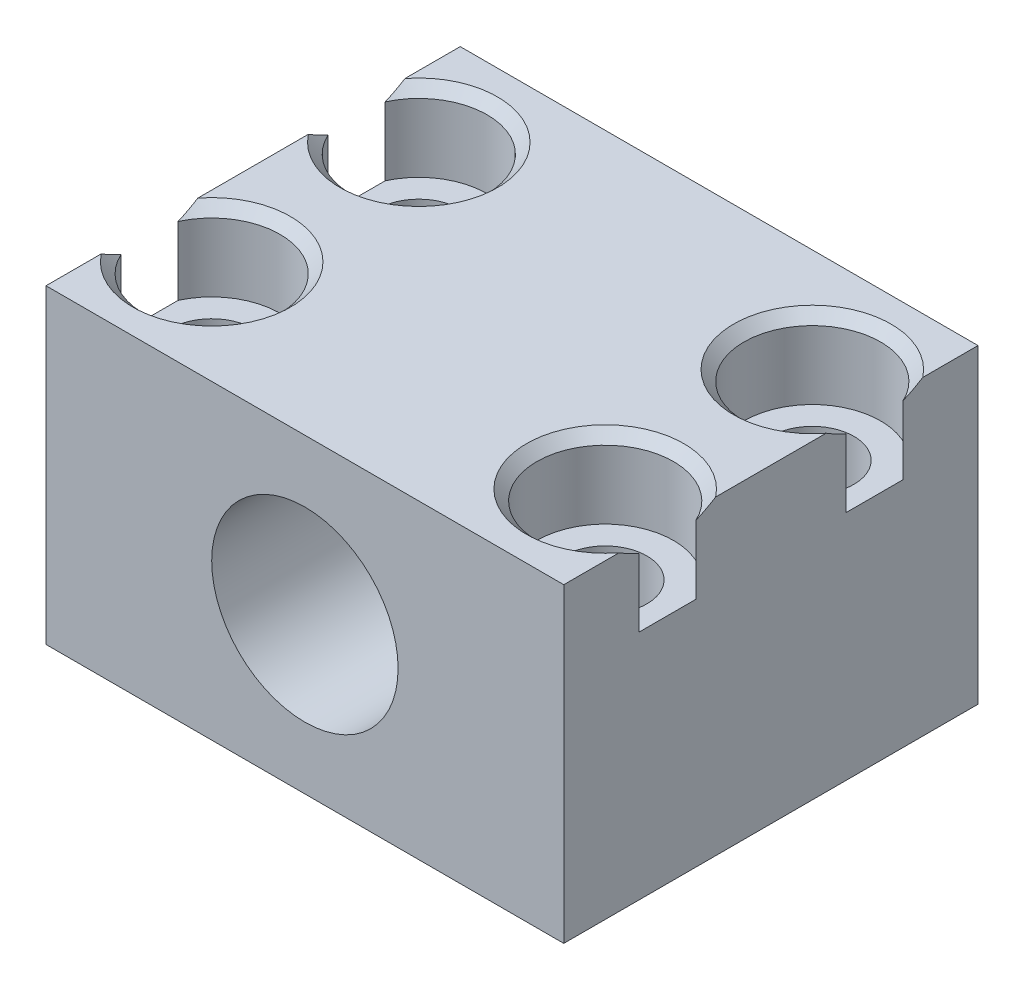
SolidWorks part; units mm, degrees
material "Gray Cast Iron"
ref_plane "Front Plane" through (0, 0, 0) normal (0, 0, 1) x (1, 0, 0)
ref_plane "Top Plane" through (0, 0, 0) normal (0, 1, 0) x (1, 0, 0)
ref_plane "Right Plane" through (0, 0, 0) normal (1, 0, 0) x (0, 0, -1)
sketch "Sketch1" plane through (0, 0, 0) normal (0, 0, 1) x (1, 0, 0)
  circle A0 centre (0, 0) radius 5.715
  circle A1 centre (0, 0) radius 18.669
  dimension "D3" = 11.43
  dimension "D1" = 37.338
extrude "nut-body-extrude" add sketch "Sketch1" along normal blind 25.4
sketch "Sketch2" plane through (0, 0, 0) normal (0, 0, 1) x (1, 0, 0)
  line L0 (0, 9.525) -> (0, 34.8179) construction
  line L1 (9.525, 0) -> (42.4926, 0) construction
  line L3 (-15.875, 9.525) -> (15.875, 9.525)
  line L4 (-15.875, 9.525) -> (-15.875, -9.525)
  line L5 (-15.875, -9.525) -> (15.875, -9.525)
  line L6 (15.875, 9.525) -> (15.875, -9.525)
  circle A1 centre (0, 0) radius 18.669
  circle A2 centre (0, 0) radius 18.669
  point P8 (-15.875, 0)
  point P9 (0, 9.525)
  dimension "D1" = 19.05
  dimension "D3" = 31.75
  dimension "D2" = 0
extrude "nut-trim-cut-extrude" cut sketch "Sketch2" along normal through all contours L3 A2 | L5 A2 | L6 A2 | L4 A2 region at (-18.141, 0, 0)
hole_wizard "CBORE for #10 Socket Head Cap Screw1" positions "Sketch5" profile "Sketch4" counterbore size "#10" standard "ANSI Inch" end condition through all
sketch "Sketch5" plane through (0, 9.525, 0) normal (0, 1, 0) x (1, 0, 0)
  line L0 (12.065, -6.35) -> (12.065, -19.05) construction
  line L1 (12.065, -19.05) -> (-12.065, -19.05) construction
  line L2 (-12.065, -19.05) -> (-12.065, -6.35) construction
  line L3 (-12.065, -6.35) -> (12.065, -6.35) construction
  line L4 (0, 0) -> (0, -12.7) construction
  line L5 (0, -12.7) -> (15.875, -12.7) construction
  line L6 (15.875, -25.4) -> (15.875, 0) construction
  line L7 (-5.715, 0) -> (-5.715, -25.4) construction
  line L8 (-5.715, 0) -> (-5.715, -25.4) construction
  line L9 (5.715, 0) -> (5.715, -25.4) construction
  point P0 (12.065, -6.35)
  point P2 (12.065, -19.05)
  point P4 (-12.065, -19.05)
  point P6 (-12.065, -6.35)
  point P29 (12.065, -12.7)
  point P43 (0, -6.35)
  dimension "D1" = 24.13
  dimension "D2" = 12.7
sketch "Sketch4" plane through (12.065, 9.525, 6.35) normal (1, 0, 0) x (0, 0, 1)
  line L0 (0, 0) -> (0, 19.05)
  line L1 (0, 19.05) -> (2.5527, 19.05)
  line L3 (2.5527, 19.05) -> (2.5527, 4.826)
  line L4 (4.191, 4.826) -> (2.5527, 4.826)
  line L5 (4.191, 4.826) -> (4.191, 0.635)
  line L6 (4.191, 0.635) -> (4.826, 0)
  line L7 (4.826, 0) -> (0, 0)
  line L8 (-4.191, 0.635) -> (-4.826, 0) construction
  line L11 (0, -6.35) -> (0, 107.95) construction
  dimension "Thru Hole Dia." = 5.1054
  dimension "Thru Hole Depth" = 19.05
  dimension "C'Bore Dia." = 8.382
  dimension "C'Bore Depth" = 4.826
  dimension "Near C'Sink Dia." = 9.652
  dimension "Near C'Sink Angle" = 90
equation "\"dovetail-angle\" = 55"
equation "\"dovetail-stock-width\" = 5"
equation "\"dovetail-stock-height\" = 1.25"
equation "\"dovetail-depth\" = 0.5 * \"dovetail-stock-height\""
equation "\"dovetail-throat-width\" = \"dovetail-stock-width\" - (2 * \"dovetail-depth\")"
equation "\"delta-x\" = 6"
equation "\"delta-y\" = 3"
equation "\"gib-thickness\" = 0.25"
equation "\"x-slide-length\" = \"dovetail-stock-width\" + \"delta-x\""
equation "\"y-slide-length\" = \"dovetail-stock-width\" + \"delta-y\""
equation "\"dog-point-diam\" = .149"
equation "\"dog-point-length\" = .067"
equation "\"dovetail-double-height\" = 2 * \"dovetail-depth\" + 0.5"
equation "\"acme-major-diam\" = .5"
equation "\"acme-pitch-diam\" = 0.45"
equation "\"acme-minor-diam\" = 0.4"
equation "\"acme-nut-od\" = 1.47"
equation "\"acme-nut-length\" = 1"
equation "\"D3@Sketch1\"=\"acme-pitch-diam\""
equation "\"D1@Sketch1\"=\"acme-nut-od\""
equation "\"D1@nut-body-extrude\"=\"acme-nut-length\""
equation "\"acme-nut-trim-height\" = .75"
equation "\"D1@Sketch2\"=\"acme-nut-trim-height\""
equation "\"screw-bearing-od\" = 0.5"
equation "\"screw-bearing-length\" = .375"
equation "\"screw-bearing-id\" = .375"
equation "\"end-plate-thickness\" = \"screw-bearing-length\""
equation "\"screw-add-length\" = 2 * \"end-plate-thickness\" + 1 + 0.5"
equation "\"x-screw-length\" = \"x-slide-length\" + \"screw-add-length\""
equation "\"y-screw-length\" = \"y-slide-length\" + \"screw-add-length\""
equation "\"acme-nut-mount-hole-space-vert\" = 0.5 * \"acme-nut-length\""
equation "\"D2@Sketch5\"=\"acme-nut-mount-hole-space-vert\""
equation "\"vise-hole-center-dist\" = 6.75"
equation "\"wiper_plate_clearance\" = .03"
equation "\"dial-width\" = 0.5"
equation "\"quarter-twenty-free-fit\" = .2667"
equation "\"acme-nut-mount-hole-space-horz\" = 0.95"
equation "\"D1@Sketch5\"=\"acme-nut-mount-hole-space-horz\""
